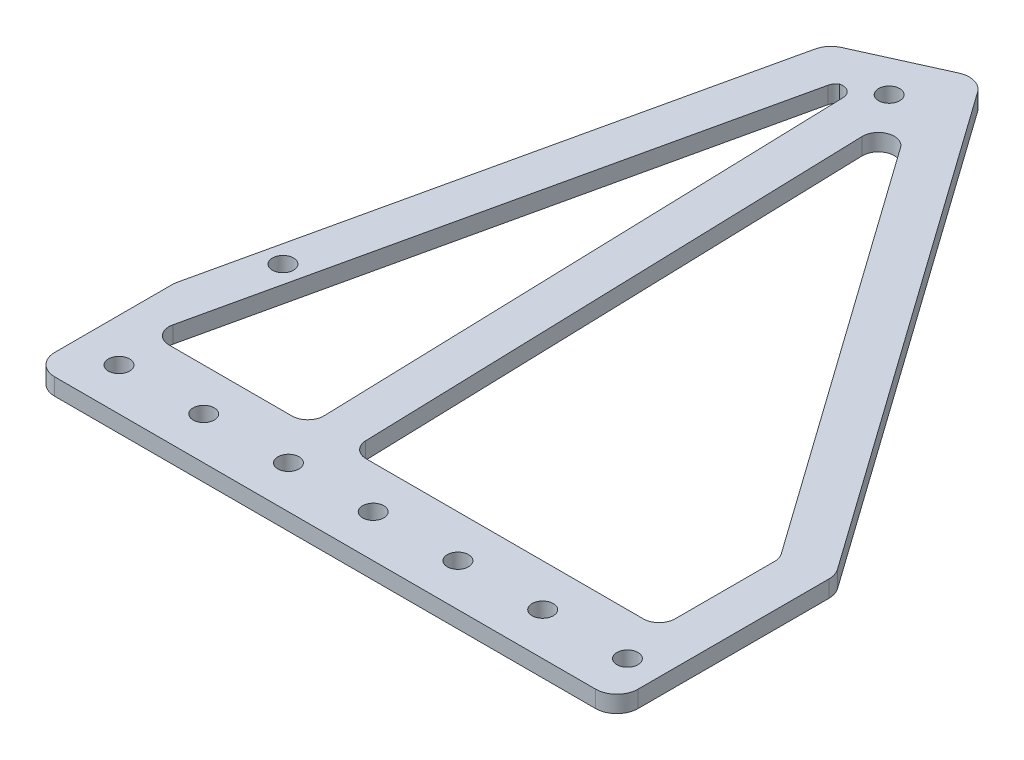
SolidWorks part; units mm, degrees
ref_plane "Front Plane" through (0, 0, 0) normal (0, 0, 1) x (1, 0, 0)
ref_plane "Top Plane" through (0, 0, 0) normal (0, 1, 0) x (1, 0, 0)
ref_plane "Right Plane" through (0, 0, 0) normal (1, 0, 0) x (0, 0, -1)
sketch "Sketch1" plane through (0, 0, 0) normal (0, 1, 0) x (1, 0, 0)
  line L0 (-67.5, 116.9134) -> (-64, 0) construction
  line L2 (-16, -8) -> (6, -8)
  line L6 (-63.5135, 117.4231) -> (-2, 30.797)
  line L8 (-81.5242, 119.3123) -> (-61.4758, 128.3709)
  line L9 (-61.4758, 128.3709) -> (6, 33.3484)
  line L10 (-67.5, 116.9134) -> (0, 0) construction
  line L11 (-67.5, 116.9134) -> (-71.5, 123.8416) construction
  line L13 (6, -8) -> (-16, -8) construction
  line L17 (-2, 30.797) -> (-2, 8)
  line L23 (-81.5242, 119.3123) -> (-104.1269, 18.5896)
  line L24 (-104.1269, -8) -> (-86.0937, -8)
  line L27 (-86.0937, -8) -> (-16, -8)
  line L28 (-104.1269, -8) -> (-104.1269, 18.5896)
  line L29 (-96, 0) -> (-97.0217, 31.9837) construction
  line L33 (-2, 8) -> (-60.2377, 8)
  line L37 (6, 33.3484) -> (6, -8)
  line L38 (-60.2377, 8) -> (-63.5135, 117.4231)
  line L48 (-68.2413, 8) -> (-98.3042, 8)
  line L49 (-98.3042, 8) -> (-74.5924, 113.6656)
  line L50 (-74.5924, 113.6656) -> (-71.4471, 115.0868)
  line L52 (-71.4471, 115.0868) -> (-68.2413, 8)
  circle A0 centre (-16, 0) radius 2
  circle A2 centre (0, 0) radius 2
  circle A3 centre (-67.5, 116.9134) radius 2
  circle A4 centre (-32, 0) radius 2
  circle A5 centre (-48, 0) radius 2
  circle A6 centre (-64, 0) radius 2
  circle A7 centre (-80, 0) radius 2
  circle A8 centre (-96, 0) radius 2
  circle A11 centre (-97.0217, 31.9837) radius 2
  point P4 (0, 0)
  point P7 (0, 0)
  point P20 (-63.4802, 109.951)
  dimension "D2" = 4
  dimension "D15" = 4
  dimension "D3" = 4
  dimension "D4" = 6
  dimension "D5" = 4
  dimension "D6" = 8
  dimension "D7" = 135
  dimension "D8" = 8
  dimension "D9" = 8
  dimension "D10" = 8
  dimension "D12" = 32
  dimension "D13" = 16
  dimension "D14" = 8
  dimension "D11" = 6
extrude "Boss-Extrude1" add sketch "Sketch1" along normal blind 3.18
fillet "Fillet2" radius 4 6 edges at (-61.4758, 1.59, -128.3709) (-81.5242, 1.59, -119.3123) (-104.1269, 1.59, 8) (-104.1269, 1.59, -18.5896) (6, 1.59, 8) (6, 1.59, -33.3484)
fillet "Fillet4" radius 3 6 edges at (-2, 1.59, -8) (-2, 1.59, -30.797) (-60.2377, 1.59, -8) (-98.3042, 1.59, -8) (-63.5135, 1.59, -117.4231) (-68.2413, 1.59, -8)
fillet "Fillet5" radius 2 2 edges at (-71.4471, 1.59, -115.0868) (-74.5924, 1.59, -113.6656)
